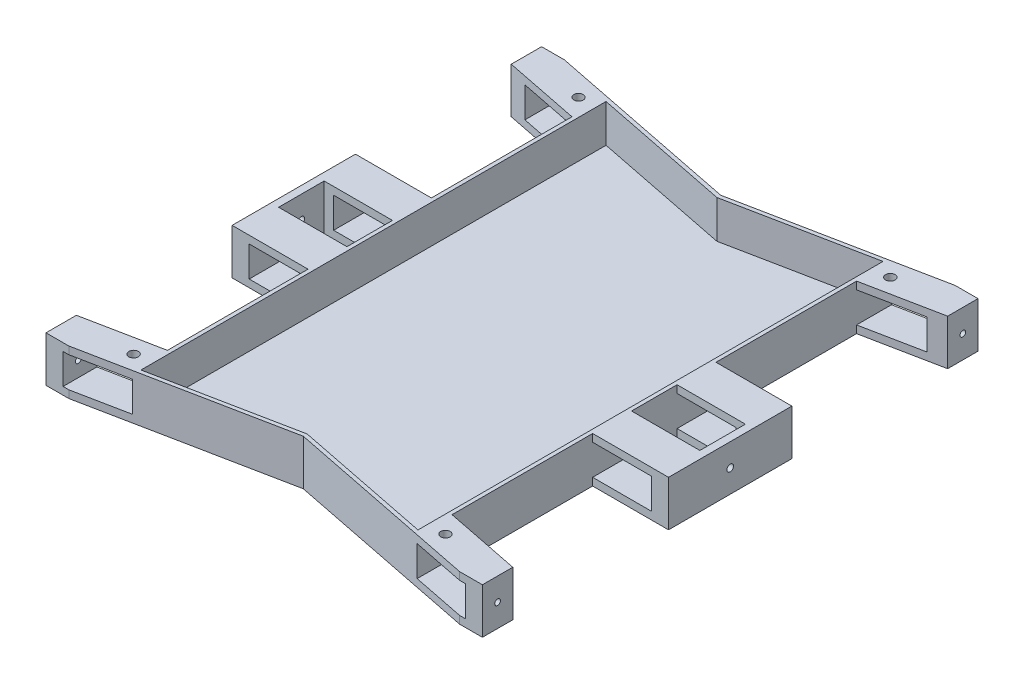
SolidWorks part; units mm, degrees
ref_plane "Front Plane" through (0, 0, 0) normal (0, 0, 1) x (1, 0, 0)
ref_plane "Top Plane" through (0, 0, 0) normal (0, 1, 0) x (1, 0, 0)
ref_plane "Right Plane" through (0, 0, 0) normal (1, 0, 0) x (0, 0, -1)
sketch "Sketch1" plane through (0, 0, 0) normal (0, 1, 0) x (1, 0, 0)
  line L1 (-55, 0) -> (55, 0) construction
  line L2 (115, 32.5) -> (115, -32.5)
  line L3 (115, -32.5) -> (75, -32.5)
  line L4 (75, -32.5) -> (75, -106.6)
  line L5 (75, -106.6) -> (115, -114.6)
  line L6 (115, -114.6) -> (115, -130.6)
  line L7 (115, -130.6) -> (103, -130.6)
  line L8 (103, -130.6) -> (0, -110)
  line L9 (0, -55) -> (0, 55) construction
  line L11 (-115, 32.5) -> (-115, -32.5)
  line L12 (-115, -32.5) -> (-75, -32.5)
  line L13 (-75, -32.5) -> (-75, -106.6)
  line L14 (-75, -106.6) -> (-115, -114.6)
  line L15 (-115, -114.6) -> (-115, -130.6)
  line L16 (-115, -130.6) -> (-103, -130.6)
  line L17 (-103, -130.6) -> (0, -110)
  line L18 (115, 32.5) -> (75, 32.5)
  line L19 (75, 32.5) -> (75, 106.6)
  line L20 (115, 130.6) -> (103, 130.6)
  line L21 (115, 114.6) -> (115, 130.6)
  line L22 (75, 106.6) -> (115, 114.6)
  line L23 (103, 130.6) -> (0, 110)
  line L24 (-115, 114.6) -> (-115, 130.6)
  line L25 (-115, 130.6) -> (-103, 130.6)
  line L26 (-103, 130.6) -> (0, 110)
  line L27 (-75, 106.6) -> (-115, 114.6)
  line L28 (-115, 32.5) -> (-75, 32.5)
  line L29 (-75, 32.5) -> (-75, 106.6)
  line L30 (75, -106.6) -> (75, -125) construction
  line L32 (-75, -106.6) -> (-75, -125) construction
  line L34 (-75, 106.6) -> (-75, 125) construction
  line L36 (75, 106.6) -> (75, 125) construction
  point P21 (115, 0)
  point P33 (-115, 0)
  dimension "D1" = 250
  dimension "D2" = 220
  dimension "D3" = 150
  dimension "D4" = 16
  dimension "D5" = 12
  dimension "D6" = 65
  dimension "D7" = 40
extrude "Boss-Extrude1" add sketch "Sketch1" along normal blind 12 and the other way blind 12
sketch "Sketch2" plane through (0, 0, 130.6) normal (0, 0, 1) x (1, 0, 0)
  line L0 (-115, -12) -> (-115, 12) construction
  line L1 (-106, -8) -> (106, -8)
  line L2 (-106, -8) -> (-106, 8)
  line L3 (-106, 8) -> (106, 8)
  line L4 (106, -8) -> (106, 8)
  line L5 (115, -12) -> (115, 12) construction
  line L7 (55, 0) -> (-55, 0) construction
  dimension "D1" = 8
  dimension "D2" = 8
  dimension "D3" = 9
  dimension "D4" = 9
extrude "Cut-Extrude1" cut sketch "Sketch2" against normal blind 320
sketch "Sketch4" plane through (0, 12, 0) normal (0, 1, 0) x (1, 0, 0)
  line L0 (-55, 0) -> (55, 0) construction
  line L1 (-111, 12) -> (-75, 12)
  line L2 (-111, 12) -> (-111, -12)
  line L3 (-111, -12) -> (-75, -12)
  line L4 (-75, 12) -> (-75, -12)
  line L5 (-115, 32.5) -> (-115, -32.5) construction
  line L6 (-75, -32.5) -> (-75, -106.6) construction
  line L7 (0, -55) -> (0, 55) construction
  line L8 (111, -12) -> (75, -12)
  line L9 (75, 12) -> (75, -12)
  line L10 (111, 12) -> (75, 12)
  line L11 (111, 12) -> (111, -12)
  dimension "D1" = 12
  dimension "D2" = 12
  dimension "D3" = 4
extrude "Cut-Extrude2" cut sketch "Sketch4" against normal blind 24
sketch "Sketch6" plane through (0, 0, 0) normal (1, 0, 0) x (0, 0, -1)
  line L0 (-114.6, 0) -> (-130.6, 0) construction
  line L1 (114.6, 0) -> (130.6, 0) construction
  circle A0 centre (-122.6, 0) radius 1.5
  circle A1 centre (122.6, 0) radius 1.5
  point P6 (-122.6, 0)
  point P10 (122.6, 0)
  dimension "D1" = 3
extrude "Cut-Extrude3" cut sketch "Sketch6" against normal through all both and the other way through all
sketch "Sketch7" plane through (115, 0, 0) normal (1, 0, 0) x (0, 0, -1)
  circle A0 centre (0, 0) radius 1.75
  dimension "D1" = 3.5
extrude "Cut-Extrude4" cut sketch "Sketch7" against normal up to surface (230 mm away) up to face at (-115, 0, 0)
sketch "Sketch8" plane through (0, 12, 0) normal (0, 1, 0) x (1, 0, 0)
  line L0 (0, 110) -> (0, -110) construction
  line L1 (106, -12) -> (106, 12) construction
  line L2 (106, 8) -> (94, 8)
  line L3 (106, 8) -> (106, -8)
  line L4 (106, -8) -> (94, -8)
  line L5 (94, 8) -> (94, -8)
  line L6 (-106, 0) -> (115, 0) construction
  line L7 (-106, 12) -> (-106, -12) construction
  line L8 (115, -32.5) -> (115, 32.5) construction
  line L9 (-106, -8) -> (-94, -8)
  line L10 (-94, 8) -> (-94, -8)
  line L11 (-106, 8) -> (-94, 8)
  line L12 (-106, 8) -> (-106, -8)
  point P16 (94, 0)
  dimension "D1" = 16
  dimension "D2" = 12
extrude "Cut-Extrude5" [suppressed] cut sketch "Sketch8" against normal up to surface (5 mm away) up to face at (0, 8, 0)
sketch "Sketch11" plane through (0, 12, 0) normal (0, 1, 0) x (1, 0, 0)
  line L0 (-75, -125) -> (-75, 125)
  line L1 (-103, -130.6) -> (0, -110) construction
  line L2 (0, 110) -> (-103, 130.6) construction
  line L3 (75, 125) -> (75, -125)
  line L4 (103, 130.6) -> (0, 110) construction
  line L5 (0, -110) -> (103, -130.6) construction
  line L6 (75, 32.5) -> (75, 106.6) construction
  line L7 (-75, 106.6) -> (-75, 32.5) construction
  line L8 (0, -110) -> (75, -125)
  line L9 (-75, -125) -> (0, -110)
  line L10 (0, 110) -> (-75, 125)
  line L11 (75, 125) -> (0, 110)
extrude "Cut-Extrude7" cut sketch "Sketch11" against normal up to surface (4 mm away) up to face at (0, 8, 0)
sketch "Sketch12" plane through (0, -8, 0) normal (0, 1, 0) x (1, 0, 0)
  line L0 (-75, 125) -> (-75, -125)
  line L1 (-103, -130.6) -> (0, -110) construction
  line L2 (75, 125) -> (75, -125)
  line L3 (-75, -125) -> (0, -110)
  line L4 (0, -110) -> (75, -125)
  line L5 (-75, 125) -> (0, 110)
  line L6 (0, 110) -> (75, 125)
  line L7 (0, 107.9604) -> (73, 122.5604)
  line L8 (73, 122.5604) -> (73, -122.5604)
  line L9 (0, -107.9604) -> (73, -122.5604)
  line L10 (-73, -122.5604) -> (0, -107.9604)
  line L11 (-73, 122.5604) -> (-73, -122.5604)
  line L12 (-73, 122.5604) -> (0, 107.9604)
  dimension "D1" = 2
extrude "Boss-Extrude2" add sketch "Sketch12" along normal blind 20
sketch "Sketch14" plane through (0, 12, 0) normal (0, 1, 0) x (1, 0, 0)
  line L0 (0, 110) -> (0, -110) construction
  line L1 (75, 0) -> (-75, 0) construction
  line L2 (75, -12) -> (75, 12) construction
  line L3 (-75, 12) -> (-75, -12) construction
  line L4 (-83.9461, 108.3892) -> (-80.4076, 126.0815) construction
  line L5 (-115, 114.6) -> (-75, 106.6) construction
  line L6 (0, 110) -> (-103, 130.6) construction
  circle A0 centre (-82.1768, 117.2354) radius 2.5
  circle A1 centre (82.1768, 117.2354) radius 2.5
  circle A2 centre (82.1768, -117.2354) radius 2.5
  circle A3 centre (-82.1768, -117.2354) radius 2.5
  dimension "D2" = 5
  dimension "D1" = 82
extrude "Cut-Extrude8" cut sketch "Sketch14" against normal up to next
equation "\"A\"= 4"
equation "\"D1@Boss-Extrude1\"=3*\"A\""
equation "\"D2@Boss-Extrude1\"=3*\"A\""
equation "\"D1@Sketch2\"=2*\"A\""
equation "\"D2@Sketch2\"=2*\"A\""
equation "\"D1@Sketch4\"=3*\"A\""
equation "\"D2@Sketch4\"=3*\"A\""
equation "\"D3@Sketch4\"=\"A\""
equation "\"D1@Cut-Extrude2\"=6*\"A\""
equation "\"D1@Cut-Extrude1\"=80*\"A\""
